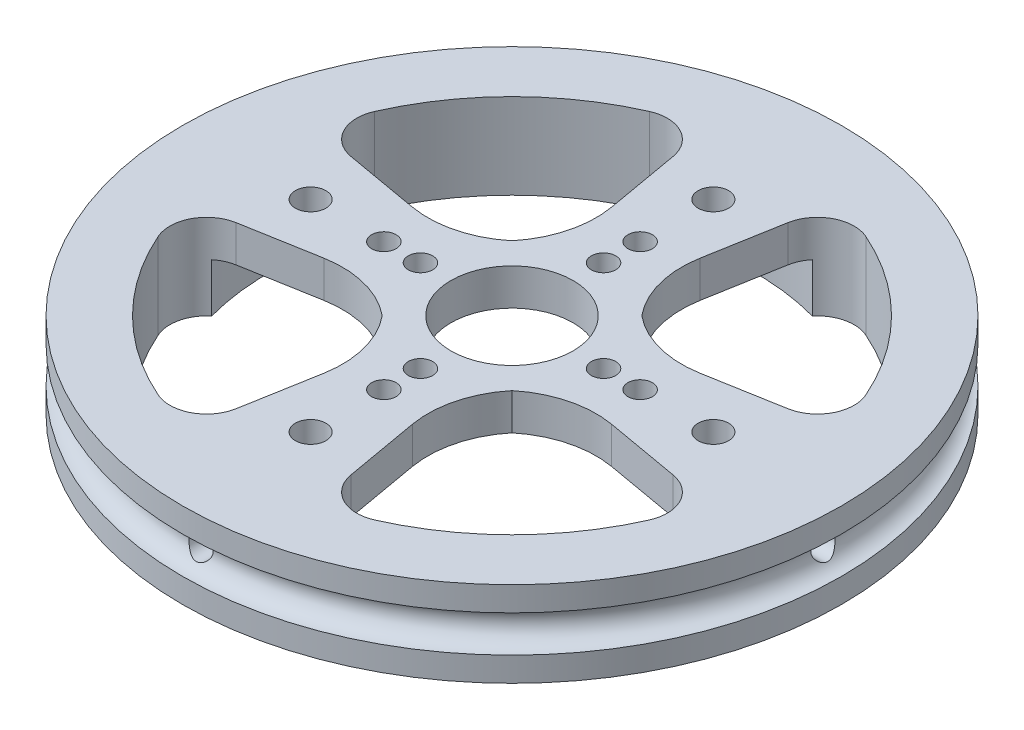
SolidWorks part; units mm, degrees
ref_plane "Front Plane" through (0, 0, 0) normal (0, 0, 1) x (1, 0, 0)
ref_plane "Top Plane" through (0, 0, 0) normal (0, 1, 0) x (1, 0, 0)
ref_plane "Right Plane" through (0, 0, 0) normal (1, 0, 0) x (0, 0, -1)
sketch "Sketch1" plane through (0, 0, 0) normal (0, 1, 0) x (1, 0, 0)
  line L0 (0, 0) -> (-7.5, 0) construction
  line L1 (-7.5, 0) -> (-10.5, 0) construction
  line L13 (-6.9685, 2.7731) -> (-21.339, 5.307)
  line L14 (-2.7731, 6.9685) -> (-5.307, 21.339)
  line L15 (6.9685, 2.7731) -> (21.339, 5.307)
  line L16 (2.7731, 6.9685) -> (5.307, 21.339)
  line L17 (2.7731, -6.9685) -> (5.307, -21.339)
  line L18 (6.9685, -2.7731) -> (21.339, -5.307)
  line L19 (-6.9685, -2.7731) -> (-21.339, -5.307)
  line L20 (-2.7731, -6.9685) -> (-5.307, -21.339)
  circle A0 centre (0, 0) radius 27
  circle A1 centre (0, 0) radius 5
  circle A3 centre (-7.5, 0) radius 1
  circle A7 centre (0, 0) radius 10.5 construction
  circle A8 centre (-10.5, 0) radius 1
  circle A9 centre (0, 10.5) radius 1
  circle A10 centre (10.5, 0) radius 1
  circle A11 centre (0, -10.5) radius 1
  arc A26 (-2.7731, 6.9685) -> (-6.9685, 2.7731) centre (0, 0) ccw construction
  arc A27 (-2.7731, 6.9685) -> (-6.9685, 2.7731) centre (0, 0) ccw
  arc A34 (-5.307, 21.339) -> (-21.339, 5.307) centre (0, 0) ccw
  arc A38 (21.339, 5.307) -> (5.307, 21.339) centre (0, 0) ccw
  arc A39 (5.307, -21.339) -> (21.339, -5.307) centre (0, 0) ccw
  arc A40 (-21.339, -5.307) -> (-5.307, -21.339) centre (0, 0) ccw
  arc A41 (6.9685, 2.7731) -> (2.7731, 6.9685) centre (0, 0) ccw
  arc A42 (2.7731, -6.9685) -> (6.9685, -2.7731) centre (0, 0) ccw
  arc A43 (-6.9685, -2.7731) -> (-2.7731, -6.9685) centre (0, 0) ccw
  circle A44 centre (0, 0) radius 7.5 construction
  circle A45 centre (0, 7.5) radius 1
  circle A46 centre (7.5, 0) radius 1
  circle A47 centre (0, -7.5) radius 1
  circle A48 centre (0, 0) radius 13.5 construction
  circle A50 centre (0, 0) radius 16.5 construction
  circle A51 centre (-16.5, 0) radius 1.25
  circle A52 centre (0, 16.5) radius 1.25
  circle A54 centre (16.5, 0) radius 1.25
  circle A56 centre (0, -16.5) radius 1.25
  point P16 (1.427, -0.078)
  point P26 (0, 0)
  point P27 (0, 0)
  point P44 (0, 0)
  point P53 (0, 0)
  point P62 (0, 0)
  point P71 (0, 0)
  point P77 (0, 0)
  point P84 (0, 0)
  dimension "D1" = 54
  dimension "D2" = 10
  dimension "D3" = 70
  dimension "D4" = 33
  dimension "D6" = 21
  dimension "D7" = 2
  dimension "D9" = 15
  dimension "D10" = 27
  dimension "D12" = 2.5
  dimension "D11" = 4
  dimension "D15" = 4
  dimension "D8" = 4
  dimension "D16" = 4
  dimension "D5" = 4
extrude "Boss-Extrude1" add sketch "Sketch1" along normal blind 2 contours A0 A56 A54 A52 A51 A47 A46 A45 A34 L14 A27 L13 A11 A10 A9 A8 A3 A1 L15 A41 L16 A38 L17 A42 L18 A39 region at (-26.2363, 0, 0)
ref_plane "Plane1" through (0, 5, 0) normal (0, 1, 0) x (1, 0, 0)
sketch "Sketch3" plane through (0, 5, 0) normal (0, 1, 0) x (1, 0, 0)
  line L0 (6.9685, -2.7731) -> (21.339, -5.307) construction
  line L1 (2.7731, -6.9685) -> (5.307, -21.339) construction
  line L6 (-2.7731, -6.9685) -> (-5.307, -21.339) construction
  line L7 (-6.9685, -2.7731) -> (-21.339, -5.307) construction
  line L9 (2.7731, 6.9685) -> (5.307, 21.339) construction
  line L44 (6.9685, 2.7731) -> (21.339, 5.307) construction
  line L45 (-2.7731, 6.9685) -> (-5.307, 21.339) construction
  line L46 (-6.9685, 2.7731) -> (-21.339, 5.307) construction
  line L47 (6.9685, -2.7731) -> (21.339, -5.307)
  line L48 (2.7731, -6.9685) -> (5.307, -21.339)
  line L49 (-2.7731, -6.9685) -> (-5.307, -21.339)
  line L50 (-6.9685, -2.7731) -> (-21.339, -5.307)
  line L51 (2.7731, 6.9685) -> (5.307, 21.339)
  line L52 (6.9685, 2.7731) -> (21.339, 5.307)
  line L53 (-2.7731, 6.9685) -> (-5.307, 21.339)
  line L54 (-6.9685, 2.7731) -> (-21.339, 5.307)
  arc A62 (5.307, -21.339) -> (21.339, -5.307) centre (0, 0) ccw construction
  circle A64 centre (0, -16.5) radius 1.25 construction
  circle A74 centre (0, 0) radius 27 construction
  circle A92 centre (0, 0) radius 27
  arc A100 (2.7731, -6.9685) -> (6.9685, -2.7731) centre (0, 0) ccw construction
  circle A101 centre (0, -7.5) radius 1 construction
  circle A102 centre (0, -10.5) radius 1 construction
  arc A103 (-21.339, -5.307) -> (-5.307, -21.339) centre (0, 0) ccw construction
  arc A104 (-6.9685, -2.7731) -> (-2.7731, -6.9685) centre (0, 0) ccw construction
  circle A105 centre (16.5, 0) radius 1.25 construction
  circle A107 centre (10.5, 0) radius 1 construction
  circle A108 centre (7.5, 0) radius 1 construction
  circle A109 centre (-7.5, 0) radius 1 construction
  circle A110 centre (-10.5, 0) radius 1 construction
  circle A112 centre (-16.5, 0) radius 1.25 construction
  circle A113 centre (0, 0) radius 5 construction
  arc A114 (6.9685, 2.7731) -> (2.7731, 6.9685) centre (0, 0) ccw construction
  arc A115 (21.339, 5.307) -> (5.307, 21.339) centre (0, 0) ccw construction
  circle A116 centre (0, 7.5) radius 1 construction
  circle A117 centre (0, 10.5) radius 1 construction
  circle A119 centre (0, 16.5) radius 1.25 construction
  arc A120 (-2.7731, 6.9685) -> (-6.9685, 2.7731) centre (0, 0) ccw construction
  arc A121 (-5.307, 21.339) -> (-21.339, 5.307) centre (0, 0) ccw construction
  arc A122 (5.307, -21.339) -> (21.339, -5.307) centre (0, 0) ccw
  circle A123 centre (0, -16.5) radius 1.25
  arc A125 (2.7731, -6.9685) -> (6.9685, -2.7731) centre (0, 0) ccw
  circle A126 centre (0, -7.5) radius 1
  circle A127 centre (0, -10.5) radius 1
  arc A128 (-21.339, -5.307) -> (-5.307, -21.339) centre (0, 0) ccw
  arc A129 (-6.9685, -2.7731) -> (-2.7731, -6.9685) centre (0, 0) ccw
  circle A130 centre (16.5, 0) radius 1.25
  circle A132 centre (10.5, 0) radius 1
  circle A133 centre (7.5, 0) radius 1
  circle A134 centre (-7.5, 0) radius 1
  circle A135 centre (-10.5, 0) radius 1
  circle A137 centre (-16.5, 0) radius 1.25
  circle A138 centre (0, 0) radius 5
  arc A139 (6.9685, 2.7731) -> (2.7731, 6.9685) centre (0, 0) ccw
  arc A140 (21.339, 5.307) -> (5.307, 21.339) centre (0, 0) ccw
  circle A141 centre (0, 7.5) radius 1
  circle A142 centre (0, 10.5) radius 1
  circle A144 centre (0, 16.5) radius 1.25
  arc A145 (-2.7731, 6.9685) -> (-6.9685, 2.7731) centre (0, 0) ccw
  arc A146 (-5.307, 21.339) -> (-21.339, 5.307) centre (0, 0) ccw
extrude "Boss-Extrude3" add sketch "Sketch3" along normal blind 2 contours A92 A134 region at (-26.2363, 5, 0)
sketch "Sketch9" plane through (0, 0, 0) normal (1, 0, 0) x (0, 0, -1)
  line L0 (-27, 5) -> (-27, 2) construction
  line L1 (27, 2) -> (-27, 2) construction
  line L2 (-27, 5) -> (0, 5)
  line L3 (-27, 5) -> (27, 5) construction
  line L4 (0, 5) -> (0, 2)
  line L5 (0, 2) -> (-27, 2)
  arc A0 (-27, 2) -> (-27, 5) centre (-27, 3.5) ccw
revolve "Revolve1" add sketch "Sketch9" angle 360 about L4 region at (0, 3.5, 12.9131)
sketch "Sketch5" plane through (0, 0, 0) normal (0, -1, 0) x (1, 0, 0)
  circle A0 centre (0, 0) radius 20
  dimension "D1" = 40
extrude "Cut-Extrude1" cut sketch "Sketch5" against normal blind 4
sketch "Sketch6" plane through (0, 0, 0) normal (1, 0, 0) x (0, 0, -1)
  line L0 (0, 3.5) -> (-27.9461, 3.5) construction
  dimension "D1" = 3.5
ref_plane "Plane2" through (0, 3.5, 27.9461) normal (0, 0, 1) x (1, 0, 0)
sketch "Sketch7" plane through (0, 3.5, 27.9461) normal (0, 0, 1) x (1, 0, 0)
  circle A0 centre (0, 0) radius 1
  dimension "D1" = 2
extrude "Cut-Extrude2" cut sketch "Sketch7" against normal blind 7
pattern_circular "CirPattern1" count 4 over 360 about axis through (0, 7, 0) along (0, 1, 0) of "Cut-Extrude2"
fillet "Fillet2" radius 2 8 edges at (21.339, 1, -5.307) (-5.307, 1, 21.339) (5.307, 1, -21.339) (-21.339, 1, 5.307) (-5.307, 1, -21.339) (21.339, 1, 5.307) (-21.339, 1, -5.307) (5.307, 1, 21.339)
sketch "Sketch10" plane through (0, 5, 0) normal (0, 1, 0) x (1, 0, 0)
  line L0 (2.7731, -6.9685) -> (5.307, -21.339) construction
  line L1 (21.339, -5.307) -> (6.9685, -2.7731) construction
  line L2 (-6.9685, -2.7731) -> (-21.339, -5.307) construction
  line L3 (-5.307, -21.339) -> (-2.7731, -6.9685) construction
  line L4 (5.307, 21.339) -> (2.7731, 6.9685) construction
  line L5 (6.9685, 2.7731) -> (21.339, 5.307) construction
  line L6 (-21.339, 5.307) -> (-6.9685, 2.7731) construction
  line L7 (-2.7731, 6.9685) -> (-5.307, 21.339) construction
  line L8 (2.7731, -6.9685) -> (5.307, -21.339)
  line L9 (21.339, -5.307) -> (6.9685, -2.7731)
  line L10 (-6.9685, -2.7731) -> (-21.339, -5.307)
  line L11 (-5.307, -21.339) -> (-2.7731, -6.9685)
  line L12 (5.307, 21.339) -> (2.7731, 6.9685)
  line L13 (6.9685, 2.7731) -> (21.339, 5.307)
  line L14 (-21.339, 5.307) -> (-6.9685, 2.7731)
  line L15 (-2.7731, 6.9685) -> (-5.307, 21.339)
  circle A0 centre (0, 0) radius 5 construction
  arc A1 (5.307, -21.339) -> (21.339, -5.307) centre (0, 0) ccw construction
  arc A2 (2.7731, -6.9685) -> (6.9685, -2.7731) centre (0, 0) ccw construction
  arc A3 (-21.339, -5.307) -> (-5.307, -21.339) centre (0, 0) ccw construction
  arc A4 (-6.9685, -2.7731) -> (-2.7731, -6.9685) centre (0, 0) ccw construction
  arc A5 (21.339, 5.307) -> (5.307, 21.339) centre (0, 0) ccw construction
  arc A6 (6.9685, 2.7731) -> (2.7731, 6.9685) centre (0, 0) ccw construction
  arc A7 (-5.307, 21.339) -> (-21.339, 5.307) centre (0, 0) ccw construction
  arc A8 (-2.7731, 6.9685) -> (-6.9685, 2.7731) centre (0, 0) ccw construction
  circle A9 centre (0, 16.5) radius 1.25 construction
  circle A11 centre (0, 10.5) radius 1 construction
  circle A12 centre (0, 7.5) radius 1 construction
  circle A13 centre (0, -16.5) radius 1.25 construction
  circle A14 centre (0, -7.5) radius 1 construction
  circle A15 centre (0, -10.5) radius 1 construction
  circle A17 centre (16.5, 0) radius 1.25 construction
  circle A19 centre (10.5, 0) radius 1 construction
  circle A20 centre (7.5, 0) radius 1 construction
  circle A21 centre (-7.5, 0) radius 1 construction
  circle A22 centre (-10.5, 0) radius 1 construction
  circle A24 centre (-16.5, 0) radius 1.25 construction
  circle A25 centre (0, 0) radius 5
  arc A26 (5.307, -21.339) -> (21.339, -5.307) centre (0, 0) ccw
  arc A27 (2.7731, -6.9685) -> (6.9685, -2.7731) centre (0, 0) ccw
  arc A28 (-21.339, -5.307) -> (-5.307, -21.339) centre (0, 0) ccw
  arc A29 (-6.9685, -2.7731) -> (-2.7731, -6.9685) centre (0, 0) ccw
  arc A30 (21.339, 5.307) -> (5.307, 21.339) centre (0, 0) ccw
  arc A31 (6.9685, 2.7731) -> (2.7731, 6.9685) centre (0, 0) ccw
  arc A32 (-5.307, 21.339) -> (-21.339, 5.307) centre (0, 0) ccw
  arc A33 (-2.7731, 6.9685) -> (-6.9685, 2.7731) centre (0, 0) ccw
  circle A34 centre (0, 16.5) radius 1.25
  circle A36 centre (0, 10.5) radius 1
  circle A37 centre (0, 7.5) radius 1
  circle A38 centre (0, -16.5) radius 1.25
  circle A39 centre (0, -7.5) radius 1
  circle A40 centre (0, -10.5) radius 1
  circle A42 centre (16.5, 0) radius 1.25
  circle A44 centre (10.5, 0) radius 1
  circle A45 centre (7.5, 0) radius 1
  circle A46 centre (-7.5, 0) radius 1
  circle A47 centre (-10.5, 0) radius 1
  circle A49 centre (-16.5, 0) radius 1.25
extrude "Cut-Extrude3" cut sketch "Sketch10" against normal blind 10
fillet "Fillet3" radius 8 8 edges at (2.7731, 5.5, 6.9685) (6.9685, 5.5, 2.7731) (-2.7731, 5.5, 6.9685) (-6.9685, 5.5, 2.7731) (-6.9685, 5.5, -2.7731) (-2.7731, 5.5, -6.9685) (2.7731, 5.5, -6.9685) (6.9685, 5.5, -2.7731)
fillet "Fillet4" radius 3 8 edges at (-21.339, 3.5, 5.307) (-5.307, 3.5, 21.339) (21.339, 3.5, 5.307) (5.307, 3.5, 21.339) (-21.339, 3.5, -5.307) (21.339, 3.5, -5.307) (-5.307, 3.5, -21.339) (5.307, 3.5, -21.339)
